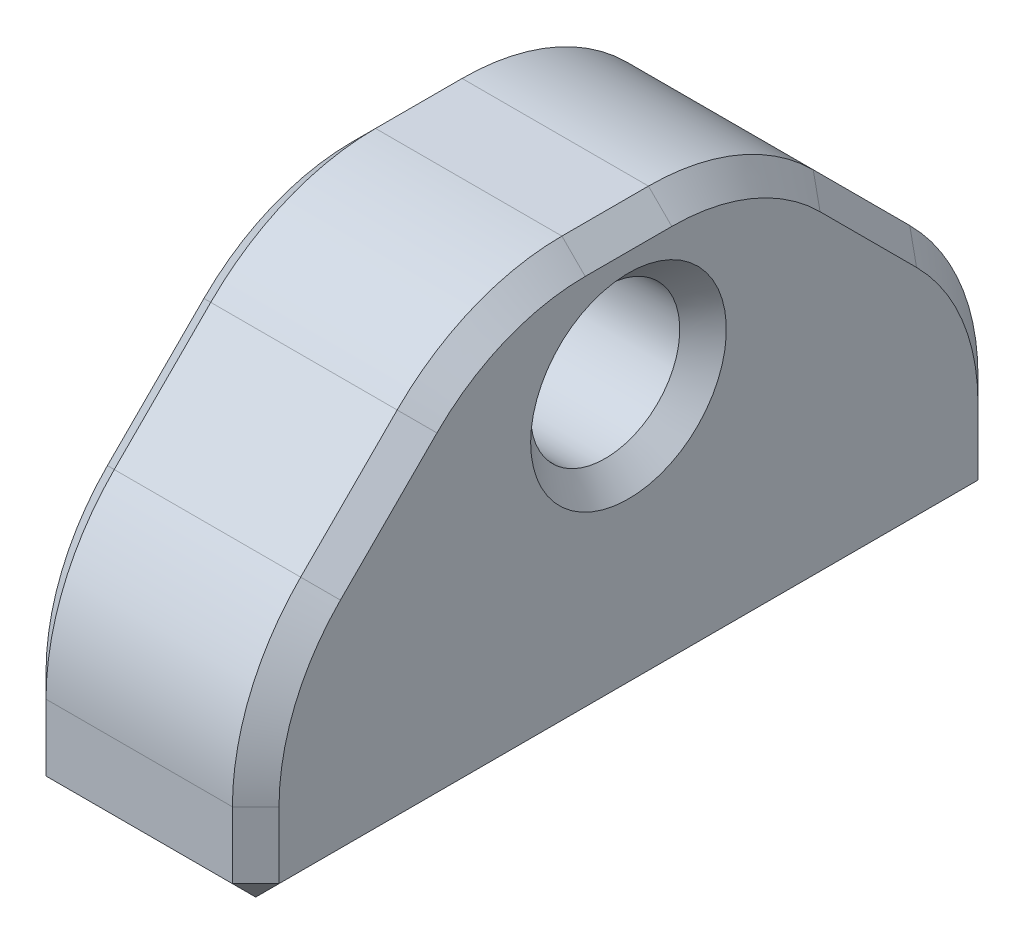
SolidWorks part; units mm, degrees
ref_plane "Front Plane" through (0, 0, 0) normal (0, 0, 1) x (1, 0, 0)
ref_plane "Top Plane" through (0, 0, 0) normal (0, 1, 0) x (1, 0, 0)
ref_plane "Right Plane" through (0, 0, 0) normal (1, 0, 0) x (0, 0, -1)
sketch "Sketch1" plane through (0, 0, 0) normal (0, 1, 0) x (1, 0, 0)
  line L0 (0, -6.35) -> (0, 6.35) construction
  line L1 (-3.175, -10.16) -> (3.175, -10.16)
  line L2 (-3.175, -10.16) -> (-3.175, 10.16)
  line L3 (-3.175, 10.16) -> (3.175, 10.16)
  line L4 (3.175, -10.16) -> (3.175, 10.16)
  line L5 (-3.175, -10.16) -> (3.175, 10.16) construction
  line L6 (-3.175, 10.16) -> (3.175, -10.16) construction
  circle A0 centre (0, 6.35) radius 2.032
  circle A1 centre (0, -6.35) radius 2.032
  point P0 (0, 0)
  point P10 (0, 0)
  dimension "D3" = 4.064
  dimension "D1" = 6.35
  dimension "D2" = 20.32
  dimension "D4" = 12.7
extrude "Boss-Extrude1" add sketch "Sketch1" along normal blind 11.43 contours L1 L4 L3 L2 A1 A0 | A1 | A0 region at (0, 0, 0) region at (0, 0, -6.35) region at (0, 0, 6.35)
extrude "Cut-Extrude1" cut sketch "Sketch1<3>" along normal blind 6.35 contours A1 | A0
sketch "Sketch1<3>" plane through (0, 0, 0) normal (0, 1, 0) x (1, 0, 0) same geometry as "Sketch1"
sketch "Sketch2" plane through (3.175, 0, 0) normal (1, 0, 0) x (0, 0, -1)
  line L0 (-10.16, 11.43) -> (-10.16, 0) construction
  circle A0 centre (0, 7.62) radius 2.032
  dimension "D1" = 4.064
  dimension "D2" = 7.62
  dimension "D3" = 10.16
extrude "Cut-Extrude2" cut sketch "Sketch2" against normal through all contours A0
chamfer "Chamfer1" distance 6.35 angle 45 2 edges at (0, 11.43, -10.16) (0, 11.43, 10.16)
fillet "Fillet1" radius 6.35 2 edges at (0, 11.43, -3.81) (0, 11.43, 3.81)
fillet "Fillet2" radius 6.35 2 edges at (0, 5.08, -10.16) (0, 5.08, 10.16)
chamfer "Chamfer2" distance 0.635 angle 45 22 edges at (3.175, 0, 0) (0, 0, -10.16) (-3.175, 0, 0) (0, 0, 10.16) (-3.175, 1.2249, -10.16) (-3.175, 4.8798, -9.6766) (-3.175, 1.2249, 10.16) (-3.175, 8.255, -6.985) (-3.175, 4.8798, 9.6766) (-3.175, 10.9466, -3.6098) (-3.175, 8.255, 6.985) (-3.175, 11.43, 0) (-3.175, 10.9466, 3.6098) (3.175, 1.2249, -10.16) (3.175, 4.8798, -9.6766) (3.175, 8.255, -6.985) (3.175, 1.2249, 10.16) (3.175, 10.9466, -3.6098) (3.175, 4.8798, 9.6766) (3.175, 11.43, 0) (3.175, 8.255, 6.985) (3.175, 10.9466, 3.6098)
chamfer "Chamfer3" distance 0.635 angle 45 4 edges at (3.175, 7.62, -2.032) (-3.175, 7.62, -2.032) (0, 0, -4.318) (0, 0, 8.382)
